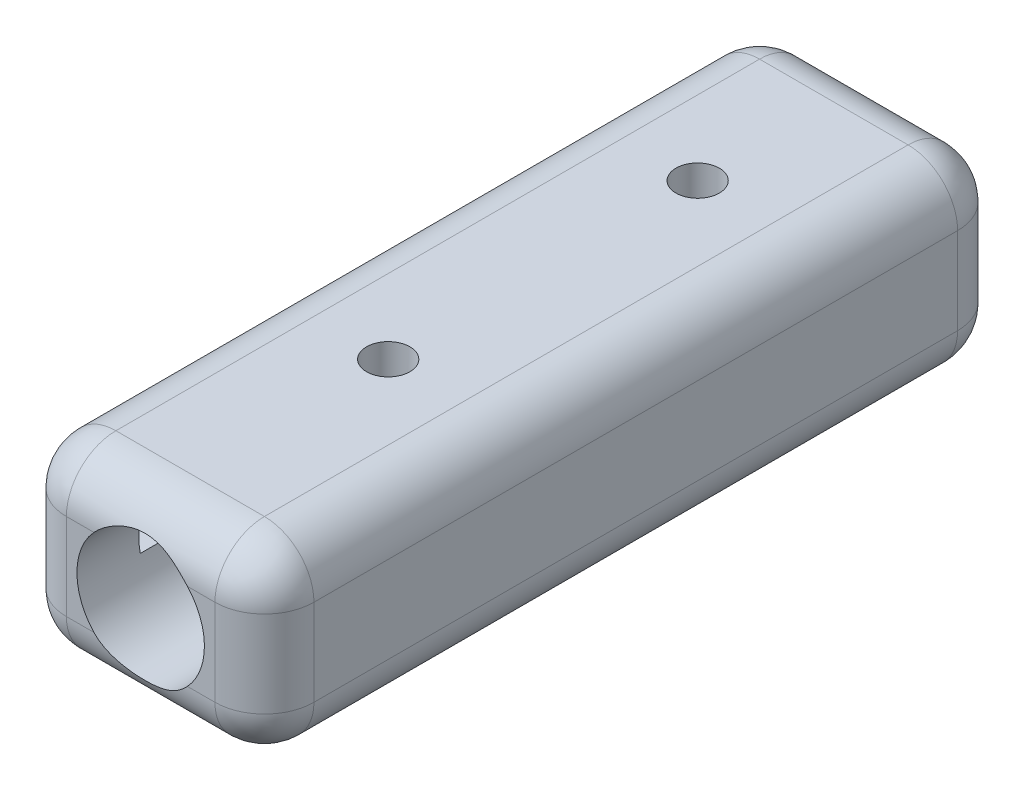
SolidWorks part; units mm, degrees
material "PLA"
ref_plane "Front" through (0, 0, 0) normal (0, 0, 1) x (1, 0, 0)
ref_plane "Top" through (0, 0, 0) normal (0, 1, 0) x (1, 0, 0)
ref_plane "Right" through (0, 0, 0) normal (1, 0, 0) x (0, 0, -1)
sketch "Sketch1" plane through (0, 0, 0) normal (0, 0, 1) x (1, 0, 0)
  line L1 (0, 0) -> (20, 0)
  line L2 (0, 0) -> (0, 15)
  line L3 (0, 15) -> (20, 15)
  line L4 (20, 0) -> (20, 15)
  dimension "D1" = 20
  dimension "D2" = 15
extrude "Boss-Extrude1" add sketch "Sketch1" along normal blind 60
sketch "Sketch2" plane through (0, 0, 60) normal (0, 0, 1) x (1, 0, 0)
  line L0 (0, 0) -> (20, 0) construction
  line L1 (0, 15) -> (0, 0) construction
  circle A0 centre (10, 7.5) radius 5.15
  point P5 (10, 0)
  point P8 (0, 7.5)
  dimension "D1" = 10.3
extrude "Cut-Extrude1" cut sketch "Sketch2" against normal blind 55
sketch "Sketch3" plane through (0, 0, 0) normal (0, 0, -1) x (-1, 0, 0)
  line L0 (-20, 15) -> (0, 15) construction
  line L1 (-17.6, 8.6) -> (-2.4, 8.6)
  line L2 (-17.6, 8.6) -> (-17.6, 6.4)
  line L3 (-17.6, 6.4) -> (-2.4, 6.4)
  line L4 (-2.4, 8.6) -> (-2.4, 6.4)
  line L5 (-20, 0) -> (-20, 15) construction
  point P6 (-10, 15)
  point P7 (-10, 8.6)
  point P10 (-20, 7.5)
  point P11 (-17.6, 7.5)
  dimension "D1" = 15.2
  dimension "D2" = 2.2
extrude "Cut-Extrude2" cut sketch "Sketch3" against normal blind 55
sketch "Sketch4" plane through (0, 15, 0) normal (0, 1, 0) x (1, 0, 0)
  line L0 (20, 0) -> (0, 0) construction
  line L1 (20, -60) -> (0, -60) construction
  circle A0 centre (10, -15) radius 1.75
  circle A1 centre (10, -40) radius 1.75
  point P7 (10, 0)
  dimension "D1" = 25
  dimension "D2" = 3.5
  dimension "D3" = 3.5
  dimension "D4" = 20
extrude "Cut-Extrude3" cut sketch "Sketch4" against normal through all
fillet "Fillet1" radius 4 8 edges at (0, 15, 30) (0, 7.5, 60) (0, 0, 30) (0, 7.5, 0) (20, 0, 30) (20, 7.5, 60) (20, 15, 30) (20, 7.5, 0)
fillet "Fillet3" radius 4 12 edges at (1.1716, 1.1716, 58.8284) (18.8284, 1.1716, 58.8284) (18.8284, 13.8284, 58.8284) (1.1716, 13.8284, 58.8284) (1.1716, 1.1716, 1.1716) (18.8284, 1.1716, 1.1716) (18.8284, 13.8284, 1.1716) (1.1716, 13.8284, 1.1716) (10, 0, 60) (10, 15, 60) (10, 0, 0) (10, 15, 0)
sketch "Sketch5" plane through (0, 0, 0) normal (0, 0, -1) x (-1, 0, 0)
  line L0 (-4, 8.6) -> (-16, 8.6) construction
  line L1 (-12, 8.6) -> (-8, 8.6)
  line L2 (-16, 6.4) -> (-4, 6.4) construction
  line L3 (-12.0025, 6.4) -> (-7.9975, 6.4)
  arc A0 (-12, 8.6) -> (-8, 8.6) centre (-10, 8.6) cw
  arc A1 (-7.9975, 6.4) -> (-12.0025, 6.4) centre (-10, 6.4) cw
  dimension "D1" = 2
  dimension "D2" = 2.0025
extrude "Cut-Extrude4" cut sketch "Sketch5" against normal up to next
